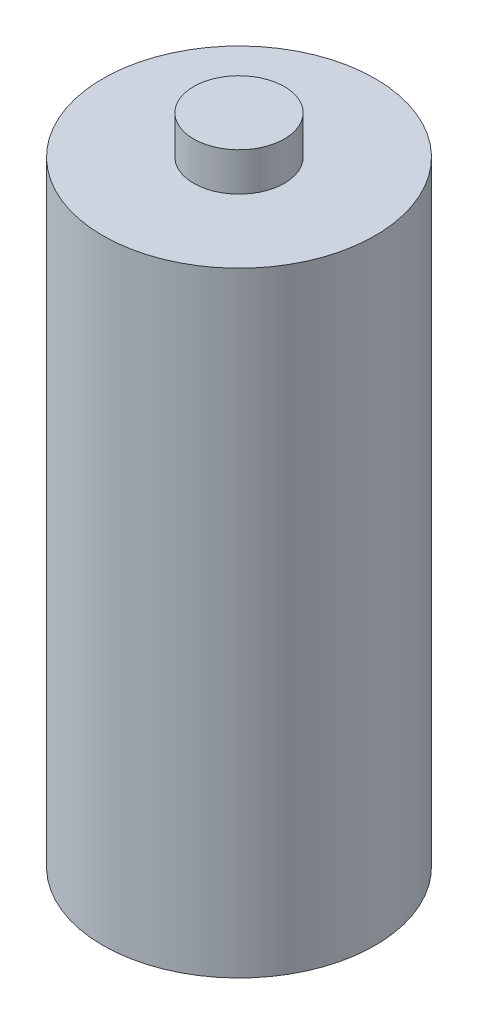
SolidWorks part; units mm, degrees
ref_plane "Front Plane" through (0, 0, 0) normal (0, 0, 1) x (1, 0, 0)
ref_plane "Top Plane" through (0, 0, 0) normal (0, 1, 0) x (1, 0, 0)
ref_plane "Right Plane" through (0, 0, 0) normal (1, 0, 0) x (0, 0, -1)
sketch "Sketch1" plane through (0, 0, 0) normal (0, 1, 0) x (1, 0, 0)
  circle A0 centre (0, 0) radius 22.5
  circle A1 centre (0, 0) radius 7.5
  dimension "D1" = 45
  dimension "D2" = 15
extrude "Boss-Extrude2" add sketch "Sketch1" along normal mid plane 114.3 contours A1
extrude "Boss-Extrude3" add sketch "Sketch1<3>" along normal mid plane 101.6 contours A0
sketch "Sketch1<3>" plane through (0, 0, 0) normal (0, 1, 0) x (1, 0, 0) same geometry as "Sketch1"
